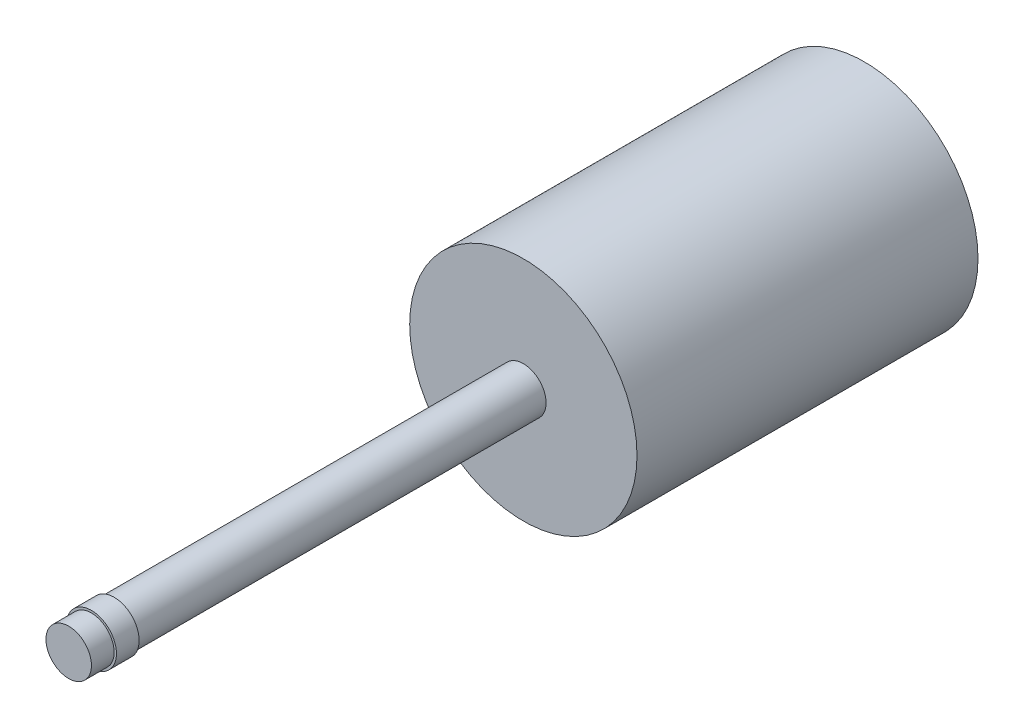
SolidWorks part; units mm, degrees
ref_plane "Front" through (0, 0, 0) normal (0, 0, 1) x (1, 0, 0)
ref_plane "Top" through (0, 0, 0) normal (0, 1, 0) x (1, 0, 0)
ref_plane "Right" through (0, 0, 0) normal (1, 0, 0) x (0, 0, -1)
sketch "Sketch2" plane through (0, 0, 0) normal (0, 0, 1) x (1, 0, 0)
  circle A0 centre (0, 0) radius 12.7
  dimension "D1" = 25.4
extrude "Boss-Extrude1" add sketch "Sketch2" along normal blind 38.1
sketch "Sketch3" plane through (0, 0, 38.1) normal (0, 0, 1) x (1, 0, 0)
  circle A0 centre (0, 0) radius 2.54
  dimension "D1" = 5.08
extrude "Boss-Extrude2" add sketch "Sketch3" along normal blind 50.8
ref_plane "Plane1" through (0, 0, 83.82) normal (0, 0, 1) x (1, 0, 0)
sketch "Sketch4" plane through (0, 0, 83.82) normal (0, 0, 1) x (1, 0, 0)
  circle A1 centre (0, 0) radius 2.794
  circle A2 centre (0, 0) radius 2.54 construction
  circle A3 centre (0, 0) radius 2.54
  dimension "D1" = 5.588
extrude "Boss-Extrude3" add sketch "Sketch4" along normal blind 2.54
